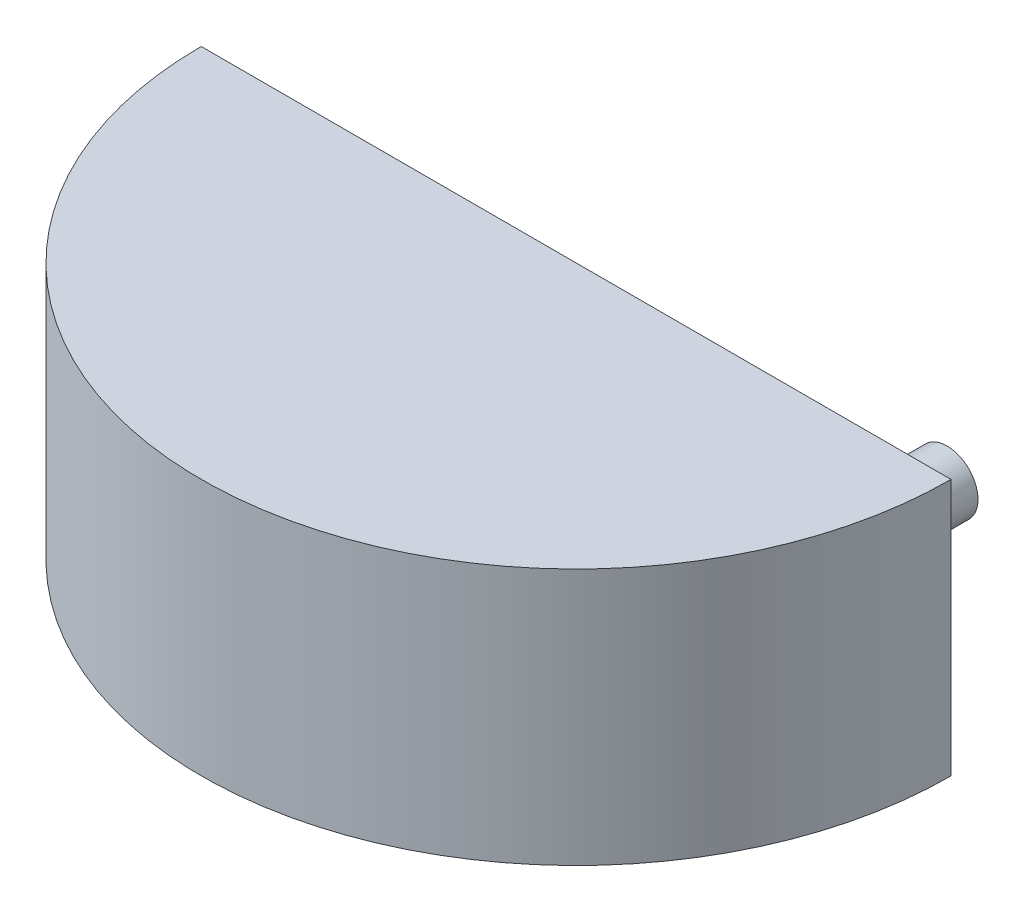
SolidWorks part; units mm, degrees
ref_plane "Front Plane" through (0, 0, 0) normal (0, 0, 1) x (1, 0, 0)
ref_plane "Top Plane" through (0, 0, 0) normal (0, 1, 0) x (1, 0, 0)
ref_plane "Right Plane" through (0, 0, 0) normal (1, 0, 0) x (0, 0, -1)
sketch "Sketch1" plane through (0, 0, 0) normal (0, 0, 1) x (1, 0, 0)
  line L0 (0, 0) -> (9.271, 0)
  line L2 (9.271, 0) -> (0, 0)
  line L3 (9.271, 0) -> (9.271, 6.35)
  line L4 (9.271, 6.35) -> (0, 6.35)
  line L5 (0, 0) -> (0, 6.35)
  line L6 (-7.6835, 1.5875) -> (7.6835, 1.5875)
  line L7 (-7.6835, 1.5875) -> (-7.6835, 4.7625)
  line L8 (-7.6835, 4.7625) -> (7.6835, 4.7625)
  line L9 (7.6835, 1.5875) -> (7.6835, 4.7625)
  line L10 (-7.6835, 1.5875) -> (7.6835, 4.7625) construction
  line L11 (-7.6835, 4.7625) -> (7.6835, 1.5875) construction
  point P5 (0, 3.175)
  dimension "D1" = 9.271
  dimension "D2" = 6.35
  dimension "D3" = 3.175
  dimension "D4" = 1.5875
revolve "Revolve1" add sketch "Sketch1" angle 360 about L5 region at (0.1124, 0.7937, 0)
sketch "Sketch2" plane through (0, 6.35, 0) normal (0, 1, 0) x (1, 0, 0)
  line L0 (-9.271, 0) -> (9.271, 0)
  line L2 (-9.271, 0) -> (10.0432, 0)
  line L3 (-9.271, 0) -> (-9.271, 10.1441)
  line L4 (-9.271, 10.1441) -> (10.0432, 10.1441)
  line L5 (10.0432, 0) -> (10.0432, 10.1441)
  circle A0 centre (0, 0) radius 9.271 construction
  circle M2 centre (0, 0) radius 9.271
extrude "Cut-Extrude1" cut sketch "Sketch2" against normal blind 9.398 contours L2 L5 L4 L3 M2 | L0 M2 region at (0, 6.35, -3.9347) region at (-9.0528, 6.35, -5.072)
sketch "Sketch3" plane through (0, 0, 0) normal (0, -1, 0) x (1, 0, 0)
  line L0 (9.271, 0) -> (-9.271, 0) construction
  circle A0 centre (5.3022, 0) radius 1.1906
  circle A1 centre (-5.3022, 0) radius 1.1906
  dimension "D1" = 2.3813
  dimension "D2" = 2.3813
  dimension "D3" = 3.9688
  dimension "D4" = 3.9688
extrude "Cut-Extrude2" cut sketch "Sketch3" against normal blind 3.048
sketch "Sketch4" plane through (0, 0, 0) normal (0, 0, -1) x (-1, 0, 0)
  line L0 (-9.271, 6.35) -> (-9.271, 0) construction
  line L1 (9.271, 6.35) -> (-9.271, 6.35) construction
  line L2 (-9.271, 0) -> (-6.4929, 0) construction
  line L3 (9.271, 0) -> (9.271, 6.35) construction
  circle A0 centre (-8.382, 5.461) radius 0.762
  circle A4 centre (-8.382, 0.889) radius 0.8255
  circle A5 centre (8.382, 5.461) radius 0.8255
  circle A6 centre (8.382, 0.889) radius 0.762
  dimension "D1" = 1.524
  dimension "D5" = 1.651
  dimension "D6" = 1.651
  dimension "D2" = 0.889
  dimension "D3" = 0.889
  dimension "D4" = 0.889
  dimension "D7" = 0.889
  dimension "D8" = 0.889
extrude "Boss-Extrude1" add sketch "Sketch4" along normal blind 0.7937
sketch "Sketch6" plane through (0, 0, -0.7937) normal (0, 0, -1) x (-1, 0, 0)
  circle A0 centre (-8.382, 0.889) radius 0.8255
  circle A1 centre (8.382, 5.461) radius 0.8255
extrude "Cut-Extrude3" cut sketch "Sketch6" against normal blind 1.5875
sketch "Sketch7" plane through (0, 0, 0) normal (0, -1, 0) x (1, 0, 0)
  line L0 (-0.7938, 0) -> (0.7937, 0)
  line L1 (0.7937, -6.35) -> (-0.7938, -6.35)
  line L2 (0.7937, -6.35) -> (0.7937, 6.35)
  line L3 (0.7937, 6.35) -> (-0.7938, 6.35)
  line L4 (-0.7938, -6.35) -> (-0.7938, 6.35)
  line L5 (0.7937, -6.35) -> (-0.7938, 6.35) construction
  line L6 (0.7937, 6.35) -> (-0.7938, -6.35) construction
  point P0 (0, 0)
  line M8 (-4.1116, 0) -> (4.1116, 0)
  dimension "D1" = 1.5875
  dimension "D2" = 12.7
extrude "Boss-Extrude2" add sketch "Sketch7" along normal blind 0.7937 contours L4 L2 L3 M8 region at (0, 0, 3.175)
